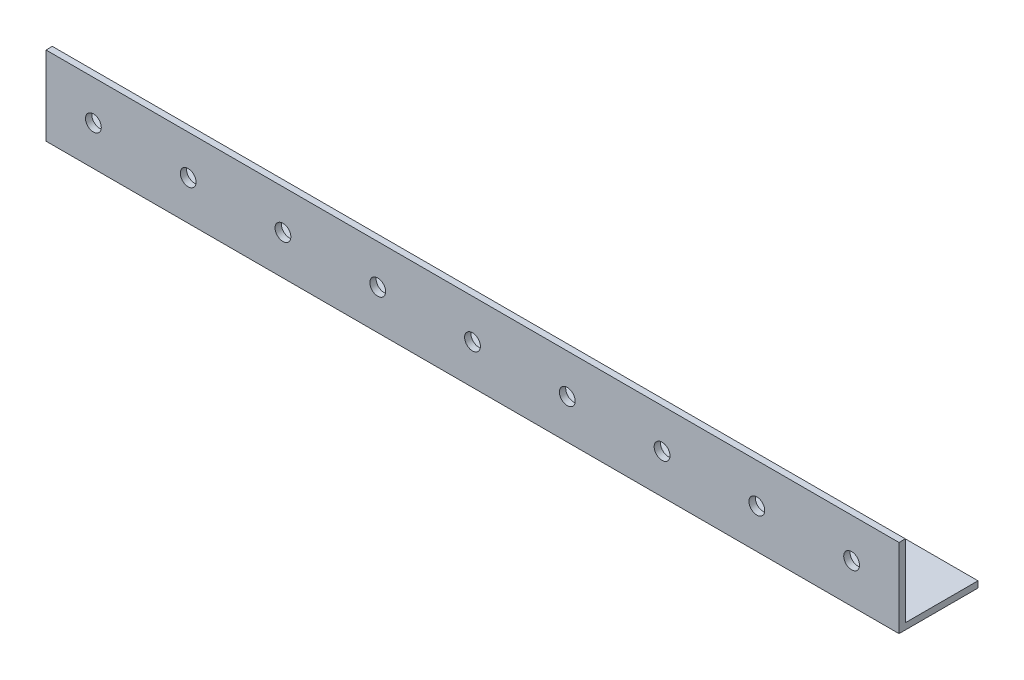
SolidWorks part; units mm, degrees
ref_plane "Спереди" through (0, 0, 0) normal (0, 0, 1) x (1, 0, 0)
ref_plane "Сверху" through (0, 0, 0) normal (0, 1, 0) x (1, 0, 0)
ref_plane "Справа" through (0, 0, 0) normal (1, 0, 0) x (0, 0, -1)
sketch "Эскиз1" plane through (0, 0, 0) normal (1, 0, 0) x (0, 0, -1)
  line L0 (0, 0) -> (0, 50)
  line L1 (0, 0) -> (50, 0)
  dimension "D1" = 50
  dimension "D2" = 50
extrude "Вытянуть-Тонкостенный1" add sketch "Эскиз1" along normal blind 540 thin thin type one direction reverse wall 4
sketch "Эскиз2" plane through (0, 0, 0) normal (0, 0, 1) x (1, 0, 0)
  circle A0 centre (30, 25) radius 5
  circle A1 centre (90, 25) radius 5
  circle A2 centre (150, 25) radius 5
  circle A3 centre (210, 25) radius 5
  circle A8 centre (270, 25) radius 5
  circle A29 centre (330, 25) radius 5
  circle A30 centre (390, 25) radius 5
  circle A31 centre (450, 25) radius 5
  circle A32 centre (510, 25) radius 5
  dimension "D1" = 9
extrude "Вырез-Вытянуть1" cut sketch "Эскиз2" against normal through all
sketch "Эскиз3" plane through (0, 0, 0) normal (0, -1, 0) x (1, 0, 0)
  circle A0 centre (30, -25) radius 5
  circle A1 centre (90, -25) radius 5
  circle A2 centre (150, -25) radius 5
  circle A3 centre (210, -25) radius 5
  circle A4 centre (270, -25) radius 5
  circle A5 centre (330, -25) radius 5
  circle A6 centre (390, -25) radius 5
  circle A7 centre (450, -25) radius 5
  circle A8 centre (510, -25) radius 5
  dimension "D1" = 9
extrude "Вырез-Вытянуть2" cut sketch "Эскиз3" against normal through all
